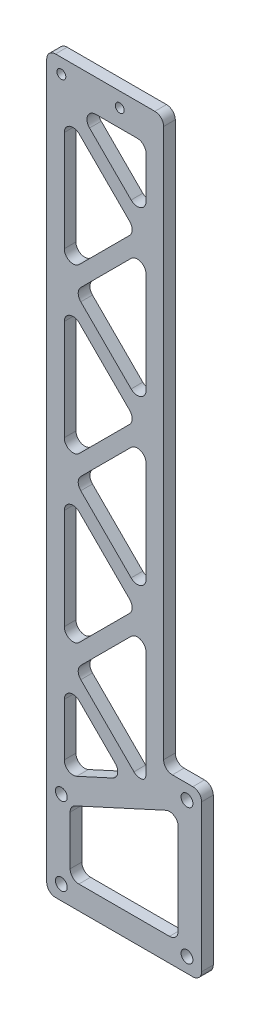
SolidWorks part; units mm, degrees
material "Thornel Mat VMA"
ref_plane "前视基准面" through (0, 0, 0) normal (0, 0, 1) x (1, 0, 0)
ref_plane "上视基准面" through (0, 0, 0) normal (0, 1, 0) x (1, 0, 0)
ref_plane "右视基准面" through (0, 0, 0) normal (1, 0, 0) x (0, 0, -1)
other "Configuration Table"
sketch "草图1" plane through (0, 0, 0) normal (0, 0, 1) x (1, 0, 0)
  line L1 (-21.5, -23.1732) -> (21.5, -23.1732) construction
  line L2 (-21.5, -23.1732) -> (-21.5, 23.1732) construction
  line L3 (-21.5, 23.1732) -> (21.5, 23.1732) construction
  line L4 (21.5, -23.1732) -> (21.5, 23.1732) construction
  line L5 (-21.5, -23.1732) -> (21.5, 23.1732) construction
  line L6 (-21.5, 23.1732) -> (21.5, -23.1732) construction
  line L8 (26.5, 221.8268) -> (-26.5, 221.8268)
  line L9 (-26.5, 221.8268) -> (-26.5, -28.1732)
  line L10 (-26.5, -28.1732) -> (26.5, -28.1732)
  line L11 (26.5, -28.1732) -> (26.5, 221.8268)
  circle A0 centre (21.5, 23.1732) radius 2.025
  circle A1 centre (21.5, -23.1732) radius 2.025
  circle A2 centre (-21.5, -23.1732) radius 2.025
  circle A3 centre (-21.5, 3.4768) radius 2.025
  point P0 (0, 0)
  dimension "D4" = 4.05
  dimension "D1" = 43
  dimension "D2" = 46.3463
  dimension "D3" = 26.65
  dimension "D5" = 5
  dimension "D6" = 5
  dimension "D7" = 5
  dimension "D9" = 250
extrude "凸台-拉伸1" add sketch "草图1" along normal blind 4
sketch "草图2" plane through (0, 0, 4) normal (0, 0, 1) x (1, 0, 0)
  line L0 (13.5, 221.8268) -> (13.5, 28.1732)
  line L1 (26.5, 221.8268) -> (-26.5, 221.8268) construction
  line L2 (13.5, 28.1732) -> (26.5, 28.1732)
  line L3 (26.5, -28.1732) -> (26.5, 221.8268) construction
  line L4 (-26.5, 221.8268) -> (-26.5, -28.1732) construction
  line L5 (13.5, 221.8268) -> (26.5, 221.8268)
  line L6 (26.5, 221.8268) -> (26.5, 28.1732)
  circle A0 centre (21.5, 23.1732) radius 2.025 construction
  dimension "D1" = 40
  dimension "D2" = 5
extrude "切除-拉伸1" cut sketch "草图2" against normal blind 4
sketch "草图4" plane through (0, 0, 4) normal (0, 0, 1) x (1, 0, 0)
  line L0 (13.5, 28.1732) -> (-26.5, 28.1732) construction
  line L1 (-26.5, 221.8268) -> (-26.5, -28.1732) construction
  line L2 (-26.5, 28.1732) -> (7.6464, 221.8268)
  line L3 (7.6464, 221.8268) -> (47.6464, 221.8268)
  line L4 (47.6464, 221.8268) -> (13.5, 28.1732)
  line L5 (13.5, 221.8268) -> (-26.5, 221.8268) construction
  line L6 (13.5, 28.1732) -> (26.5, 28.1732) construction
  line L7 (-26.5, 28.1732) -> (13.5, 28.1732)
  dimension "D1" = 80
extrude "凸台-拉伸2" [suppressed] add sketch "草图4" against normal up to surface (4 mm away)
sketch "草图5" [suppressed] plane through (0, 0, 0) normal (0, 0, -1) x (-1, 0, 0)
  line L0 (-13.5, 28.1732) -> (26.5, 28.1732) construction
  line L1 (26.5, 221.8268) -> (26.5, -28.1732) construction
  line L2 (26.5, 28.1732) -> (-7.6464, 221.8268)
  line L3 (-47.6464, 221.8268) -> (26.5, 221.8268) construction
  line L4 (-7.6464, 221.8268) -> (26.5, 221.8268)
  line L5 (26.5, 221.8268) -> (26.5, 28.1732)
  line L6 (-47.6464, 221.8268) -> (-13.5, 28.1732) construction
extrude "切除-拉伸2" [suppressed] cut sketch "草图5" against normal up to surface (4 mm away)
sketch "草图6" plane through (0, 0, 0) normal (0, 0, -1) x (-1, 0, 0)
  circle A0 centre (21.5, 216.8268) radius 1.25 construction
  circle A1 centre (1.5, 216.8268) radius 1.25 construction
  circle A2 centre (21.5, 216.8268) radius 1.25 construction
  circle A3 centre (1.5, 216.8268) radius 1.25 construction
  circle A4 centre (21.5, 216.8268) radius 1.525
  circle A5 centre (1.5, 216.8268) radius 1.525
  dimension "D1" = 3.05
extrude "切除-拉伸3" cut sketch "草图6" against normal up to surface (4 mm away) up to face at (4.5, 73.9423, 4)
fillet "圆角1" radius 3 6 edges at (26.5, 28.1732, 2) (-26.5, 221.8268, 2) (13.5, 221.8268, 2) (13.5, 28.1732, 2) (-26.5, -28.1732, 2) (26.5, -28.1732, 2)
sketch "草图7" plane through (0, 0, 4) normal (0, 0, 1) x (1, 0, 0)
  line L0 (21.5, 23.1732) -> (-21.5, 3.4768) construction
  line L1 (-21.5, 3.4768) -> (-21.5, -23.1732) construction
  line L2 (-21.5, -23.1732) -> (21.5, -23.1732) construction
  line L3 (21.5, -23.1732) -> (21.5, 23.1732) construction
  line L4 (18.5, 18.4992) -> (-18.5, 1.5513)
  line L5 (-18.5, 1.5513) -> (-18.5, -20.1732)
  line L6 (-18.5, -20.1732) -> (18.5, -20.1732)
  line L7 (18.5, -20.1732) -> (18.5, 18.4992)
  dimension "D1" = 3
extrude "切除-拉伸4" cut sketch "草图7" against normal up to surface (4 mm away) up to face at (-23.025, 216.8268, 0)
fillet "圆角2" radius 3 4 edges at (-18.5, 1.5513, 2) (18.5, 18.4992, 2) (-18.5, -20.1732, 2) (18.5, -20.1732, 2)
sketch "草图8" plane through (0, 0, 0) normal (0, 0, -1) x (-1, 0, 0)
  line L0 (-7.5, 210.8268) -> (-7.5, 22.26)
  line L1 (-7.5, 22.26) -> (20.5, 9.4345)
  line L2 (20.5, 9.4345) -> (20.5, 210.8268)
  line L3 (20.5, 210.8268) -> (-7.5, 210.8268)
  line L4 (16.7493, 2.3532) -> (-14.2507, 16.5528) construction
  line L5 (26.5, 218.8268) -> (26.5, -25.1732) construction
  line L6 (-13.5, 218.8268) -> (-13.5, 31.1732) construction
  line L7 (20.5, 210.8268) -> (-7.5, 182.8268) construction
  line L8 (-7.5, 182.8268) -> (20.5, 154.8268) construction
  line L9 (20.5, 154.8268) -> (-7.5, 126.8268) construction
  line L10 (-7.5, 126.8268) -> (20.5, 98.8268) construction
  line L11 (20.5, 98.8268) -> (-7.5, 70.8268) construction
  line L12 (-7.5, 70.8268) -> (20.5, 42.8268) construction
  line L13 (20.5, 42.8268) -> (-2.402, 19.9248) construction
  line L14 (18.7322, 212.5946) -> (-11.0355, 182.8268)
  line L15 (-11.0355, 182.8268) -> (16.9645, 154.8268)
  line L16 (16.9645, 154.8268) -> (-11.0355, 126.8268)
  line L17 (-11.0355, 126.8268) -> (16.9645, 98.8268)
  line L18 (16.9645, 98.8268) -> (-11.0355, 70.8268)
  line L19 (-11.0355, 70.8268) -> (16.9645, 42.8268)
  line L20 (16.9645, 42.8268) -> (-4.8268, 21.0355)
  line L21 (22.2678, 209.0591) -> (-3.9645, 182.8268)
  line L22 (-3.9645, 182.8268) -> (24.0355, 154.8268)
  line L23 (24.0355, 154.8268) -> (-3.9645, 126.8268)
  line L24 (-3.9645, 126.8268) -> (24.0355, 98.8268)
  line L25 (24.0355, 98.8268) -> (-3.9645, 70.8268)
  line L26 (-3.9645, 70.8268) -> (24.0355, 42.8268)
  line L27 (24.0355, 42.8268) -> (-0.6343, 18.1571)
  line L28 (16.9645, 42.8268) -> (-4.1698, 21.6926) construction
  circle A0 centre (21.5, 3.4768) radius 2.025 construction
  circle A1 centre (21.5, 216.8268) radius 1.525 construction
  dimension "D1" = 5
  dimension "D2" = 6
  dimension "D3" = 6
  dimension "D4" = 6
  dimension "D5" = 45
  dimension "D6" = 45
  dimension "D7" = 45
  dimension "D8" = 2.5
  dimension "D9" = 2.5
extrude "切除-拉伸5" cut sketch "草图8" against normal up to surface (4 mm away) contours L2 L27 L1 | L20 L19 L0 L1 | L25 L26 L2 | L18 L17 L0 | L23 L24 L2 | L16 L15 L0 | L21 L22 L2 | L14 L3 L0 region at (-0.6548, 202.672, 0) region at (-0.6548, 154.8268, 0) region at (-12.3452, 182.8268, 0) region at (-0.6548, 98.8268, 0) region at (-12.3452, 126.8268, 0) region at (-0.7186, 43.0224, 0) region at (-12.3452, 70.8268, 0) region at (-13.6743, 22.5133, 0) up to face at (-0.2692, -5.2701, 4)
fillet "圆角3" radius 3 1 edges at (4.8268, 21.0355, 2)
fillet "圆角4" radius 3 24 edges at (7.5, 123.2913, 2) (-16.9645, 98.8268, 2) (7.5, 74.3624, 2) (7.5, 67.2913, 2) (-16.9645, 42.8268, 2) (7.5, 179.2913, 2) (-16.9645, 154.8268, 2) (7.5, 130.3624, 2) (-20.5, 39.2913, 2) (-20.5, 9.4345, 2) (3.9645, 182.8268, 2) (-20.5, 207.2913, 2) (-20.5, 158.3624, 2) (-16.9645, 210.8268, 2) (7.5, 186.3624, 2) (7.5, 210.8268, 2) (3.9645, 70.8268, 2) (-20.5, 95.2913, 2) (-20.5, 46.3624, 2) (3.9645, 126.8268, 2) (-20.5, 151.2913, 2) (-20.5, 102.3624, 2) (-0.0228, 18.8141, 2) (7.5, 22.26, 2)
